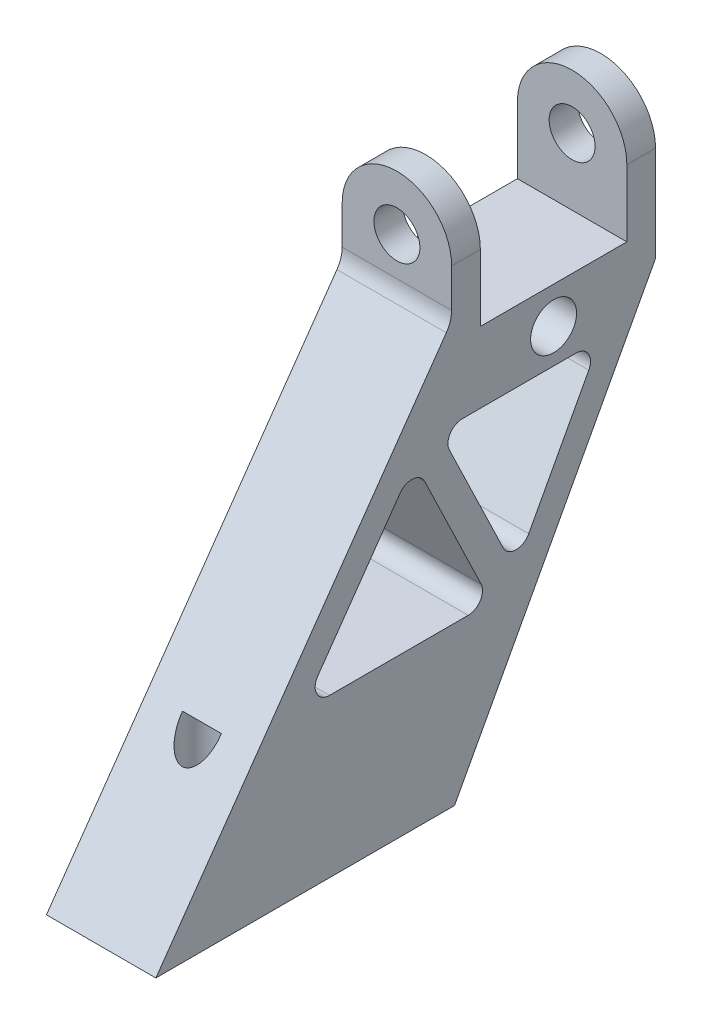
SolidWorks part; units mm, degrees
ref_plane "Front Plane" through (0, 0, 0) normal (0, 0, 1) x (1, 0, 0)
ref_plane "Top Plane" through (0, 0, 0) normal (0, 1, 0) x (1, 0, 0)
ref_plane "Right Plane" through (0, 0, 0) normal (1, 0, 0) x (0, 0, -1)
sketch "Sketch6" plane through (0, 3.4314, 0) normal (0, 1, 0) x (-1, 0, 0)
  line L0 (-13.5144, 0) -> (5.5356, 0)
  line L5 (-7.9894, 155.54) -> (0.0106, 155.54) construction
  line L8 (5.5356, 0) -> (5.5356, 133.908)
  line L9 (5.5356, 133.908) -> (-13.5144, 133.908)
  line L10 (-13.5144, 0) -> (-13.5144, 133.908)
  line L17 (-7.9894, 155.54) -> (0.0106, 155.54) construction
  line L18 (-3.9894, 155.54) -> (-3.9894, 0) construction
  dimension "D1" = 19.05
sketch3d "3DSketch1" [suppressed]
  circle A0 centre (4.1661, 92.3902, 4.7625) radius 4 construction
  circle A1 centre (4.1661, 92.3902, 4.7625) radius 4
  circle A2 centre (4.1661, 92.3902, 30.1625) radius 4 construction
  circle A3 centre (4.1661, 92.3902, 30.1625) radius 4
  point P2 (4.1661, 92.3902, 8.7625)
  point P4 (4.1661, 92.3902, 8.7625)
  point P7 (4.1661, 92.3902, 34.1625)
  point P9 (4.1661, 92.3902, 34.1625)
extrude "Boss-Extrude5" add sketch "Sketch6" along normal blind 101.6
sketch "Sketch9" plane through (0, 0, 0) normal (0, 0, -1) x (-1, 0, 0)
  line L1 (-13.5144, 105.0314) -> (6.0586, 105.0314)
  line L2 (-13.5144, 105.0314) -> (-13.5144, 87.861)
  line L3 (-13.5144, 87.861) -> (6.0586, 87.861)
  line L12 (6.0586, 105.0314) -> (6.0586, 87.861)
extrude "Cut-Extrude5" [suppressed] cut sketch "Sketch9" against normal through all
sketch "Sketch10" plane through (13.5144, 0, 0) normal (1, 0, 0) x (0, 0, -1)
  line L0 (-87, 3.4314) -> (-167.5984, 3.4314)
  line L1 (-133.908, 3.4314) -> (0, 3.4314) construction
  line L2 (-167.5984, 3.4314) -> (-168.5558, 132.8824)
  line L3 (-168.5558, 132.8824) -> (-35.5045, 117.0228)
  line L4 (-35.5045, 117.0228) -> (-35.5045, 78.3573)
  line L5 (-36.4274, 75.4376) -> (-87, 3.4314)
  line L6 (-35, 3.4314) -> (7.4334, 3.4314)
  line L7 (7.4334, 3.4314) -> (7.4334, 68.4314)
  line L8 (7.4334, 68.4314) -> (0, 68.4314)
  line L9 (0, 68.4314) -> (-35, 3.4314)
  line L10 (0, 105.0314) -> (0, 3.4314) construction
  line L12 (-30.5045, 96.7069) -> (-5, 96.7069)
  line L13 (-30.5045, 96.7069) -> (-30.5045, 73.4314)
  line L14 (-30.5045, 73.4314) -> (-5, 73.4314)
  line L15 (-5, 96.7069) -> (-5, 73.4314)
  arc A0 (-35.5045, 78.3573) -> (-36.4274, 75.4376) centre (-40.5845, 78.3573) cw
  point P22 (-30.5045, 85.0692)
  dimension "D8" = 5.08
  dimension "D1" = 5
  dimension "D2" = 5
  dimension "D3" = 65
  dimension "D4" = 35
  dimension "D5" = 52
  dimension "D6" = 25.5045
  dimension "D7" = 70
extrude "Cut-Extrude6" cut sketch "Sketch10" against normal through all
sketch "Sketch12" plane through (0, 0, 35.5045) normal (0, 0, 1) x (1, 0, 0)
  line L0 (3.9894, 3.4314) -> (3.9894, 85.0528) construction
  line L1 (7.9894, 3.4314) -> (-0.0106, 3.4314) construction
  line L2 (-5.5356, 85.0528) -> (13.5144, 85.0528) construction
  line L3 (-5.5356, 78.3573) -> (-5.5356, 105.0314) construction
  line L4 (13.5144, 78.3573) -> (13.5144, 105.0314) construction
  line L5 (13.5144, 85.0528) -> (39.9433, 85.0528)
  line L6 (39.9433, 85.0528) -> (39.9433, 114.8081)
  line L7 (39.9433, 114.8081) -> (-16.1264, 114.8081)
  line L8 (-16.1264, 114.8081) -> (-16.1264, 85.0528)
  line L9 (-16.1264, 85.0528) -> (-5.5356, 85.0528)
  circle A0 centre (3.9894, 85.0528) radius 4
  arc A1 (13.5144, 85.0528) -> (-5.5356, 85.0528) centre (3.9894, 85.0528) ccw
  dimension "D2" = 8
  dimension "D1" = 81.6214
extrude "Cut-Extrude7" cut sketch "Sketch12" against normal through all
sketch "Sketch13" plane through (0, 3.4314, 0) normal (0, -1, 0) x (1, 0, 0)
  line L0 (3.9894, 87) -> (3.9894, 69.5) construction
  line L1 (-5.5356, 87) -> (13.5144, 87) construction
  line L2 (3.9894, 155.54) -> (3.9894, 0) construction
  line L3 (3.9894, 69.5) -> (3.9894, 42.5) construction
  dimension "D1" = 17.5
  dimension "D2" = 27
sketch "Sketch14" plane through (0, 3.4314, 0) normal (0, -1, 0) x (1, 0, 0)
  circle A0 centre (3.9894, 69.5) radius 3.4
  circle A1 centre (3.9894, 42.5) radius 3.4
  dimension "D1" = 6.8
extrude "Cut-Extrude8" cut sketch "Sketch14" against normal blind 25
thread "Thread1" pitch 1.25 method cut profile "Thread Profile1" start angle 0, offset 0, length 15, pitch 1.25, diameter 6.8
ref_plane "Plane1" through (7.3894, 3.4314, 42.5) normal (0, 0, 1) x (1, 0, 0)
sketch "Thread Profile1" plane through (7.3894, 3.4314, 42.5) normal (0, 0, 1) x (1, 0, 0)
  line L0 (0, 0) -> (0, 1.25) construction
  line L1 (0, 0) -> (0.6766, 0.3906)
  line L2 (0.6766, 0.3906) -> (0.6766, 0.5469)
  line L3 (0.6766, 0.5469) -> (0, 0.9375)
  line L4 (0.6766, 0.4687) -> (0, 0.4687) construction
  line L11 (0, 0) -> (0, 0.9375)
  point P2 (0, 0)
  dimension "Pitch" = 1.25
  dimension "Profile_Angle" = 60
  dimension "Profile_Land" = 0.1562
  dimension "Profile_Height" = 0.6766
thread "Thread2" pitch 1.25 method cut profile "Thread Profile2" start angle 0, offset 0, length 15, pitch 1.25, diameter 6.8
ref_plane "Plane2" through (7.3894, 3.4314, 69.5) normal (0, 0, 1) x (1, 0, 0)
sketch "Thread Profile2" plane through (7.3894, 3.4314, 69.5) normal (0, 0, 1) x (1, 0, 0)
  line L0 (0, 0) -> (0, 1.25) construction
  line L1 (0, 0) -> (0.6766, 0.3906)
  line L2 (0.6766, 0.3906) -> (0.6766, 0.5469)
  line L3 (0.6766, 0.5469) -> (0, 0.9375)
  line L4 (0.6766, 0.4687) -> (0, 0.4687) construction
  line L11 (0, 0) -> (0, 0.9375)
  point P2 (0, 0)
  dimension "Pitch" = 1.25
  dimension "Profile_Angle" = 60
  dimension "Profile_Land" = 0.1562
  dimension "Profile_Height" = 0.6766
sketch "Sketch19" plane through (13.5144, 0, 0) normal (1, 0, 0) x (0, 0, -1)
  line L0 (-17.7522, 73.4314) -> (-17.7522, 67.0814) construction
  line L1 (-30.5045, 73.4314) -> (-5, 73.4314) construction
  circle A0 centre (-17.7522, 67.0814) radius 4
  dimension "D1" = 6.35
  dimension "D2" = 8
extrude "Cut-Extrude9" cut sketch "Sketch19" against normal through all
sketch "Sketch20" plane through (13.5144, 0, 0) normal (1, 0, 0) x (0, 0, -1)
  line L0 (-69.4416, 28.4314) -> (-21.5385, 28.4314) construction
  line L1 (-87, 3.4314) -> (-36.4274, 75.4376) construction
  line L2 (0, 68.4314) -> (-35, 3.4314) construction
  line L3 (-87, 3.4314) -> (-35, 3.4314) construction
  line L4 (-44.4946, 55.2518) -> (-58.8107, 34.8683)
  line L5 (-56.7649, 30.9314) -> (-32.6261, 30.9314)
  line L6 (-22.0819, 37.9685) -> (-11.6208, 57.3962)
  line L7 (-13.822, 61.0814) -> (-33.6452, 61.0814)
  line L8 (-40.4002, 61.0814) -> (-25.8711, 30.9314) construction
  line L9 (-35.8974, 57.4961) -> (-26.5352, 38.0684)
  line L10 (-40.1967, 54.9002) -> (-30.374, 34.5167)
  circle A0 centre (-17.7522, 67.0814) radius 4 construction
  arc A1 (-58.8107, 34.8683) -> (-56.7649, 30.9314) centre (-56.7649, 33.4314) ccw
  arc A2 (-40.1967, 54.9002) -> (-44.4946, 55.2518) centre (-42.4488, 53.8149) ccw
  arc A3 (-30.374, 34.5167) -> (-32.6261, 30.9314) centre (-32.6261, 33.4314) cw
  arc A4 (-35.8974, 57.4961) -> (-33.6452, 61.0814) centre (-33.6452, 58.5814) cw
  arc A5 (-26.5352, 38.0684) -> (-22.0819, 37.9685) centre (-24.2831, 39.1537) ccw
  arc A6 (-11.6208, 57.3962) -> (-13.822, 61.0814) centre (-13.822, 58.5814) ccw
  dimension "D8" = 2.5
  dimension "D1" = 25
  dimension "D2" = 5
  dimension "D3" = 6
  dimension "D4" = 2.5
  dimension "D5" = 2.5
  dimension "D6" = 5
  dimension "D7" = 5
extrude "Cut-Extrude10" cut sketch "Sketch20" against normal up to next
